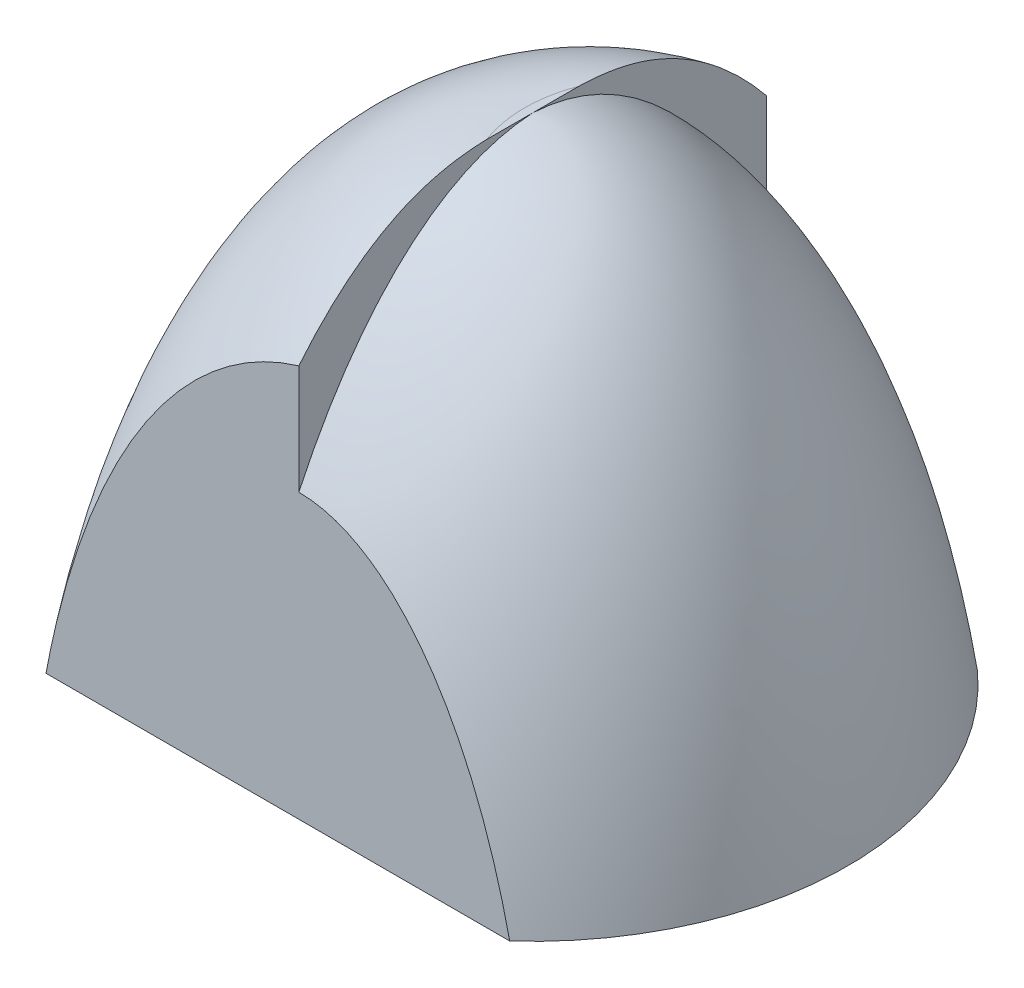
SolidWorks part; units mm, degrees
ref_plane "Front Plane" through (0, 0, 0) normal (0, 0, 1) x (1, 0, 0)
ref_plane "Top Plane" through (0, 0, 0) normal (0, 1, 0) x (1, 0, 0)
ref_plane "Right Plane" through (0, 0, 0) normal (1, 0, 0) x (0, 0, -1)
sketch "Sketch1" plane through (0, 0, 0) normal (0, 0, 1) x (1, 0, 0)
  line L0 (0, 0) -> (91.3948, 0) construction
  line L1 (0, -274.9226) -> (0, 50480.6925) construction
  ellipse E0 centre (0, 0) end of major axis (0, 712.2672) minor radius 343.2806
extrude "Boss-Extrude1" add sketch "Sketch1" along normal blind 237.5 and the other way blind 237.5
sketch "Sketch7" plane through (0, 0, 237.5) normal (0, 0, 1) x (1, 0, 0)
  line L1 (-553.6267, 209.5972) -> (494.8512, 209.5972)
  line L2 (-553.6267, 209.5972) -> (-553.6267, -734.6018)
  line L3 (-553.6267, -734.6018) -> (494.8512, -734.6018)
  line L4 (494.8512, 209.5972) -> (494.8512, -734.6018)
  line L5 (-553.6267, 209.5972) -> (494.8512, -734.6018) construction
  line L6 (-553.6267, -734.6018) -> (494.8512, 209.5972) construction
  ellipse E0 centre (0, 0) end of major axis (0, 712.2672) minor radius 343.2806 construction
  point P0 (-29.3877, -262.5023)
  point P6 (0, 712.2672)
  dimension "D1" = 502.67
extrude "Cut-Extrude2" cut sketch "Sketch7" against normal through all contours L1 L4 L3 L2
sketch "Sketch11" plane through (0, 0, 0) normal (0, 0, 1) x (1, 0, 0)
  line L0 (-343.2806, 0) -> (-743.2267, 0)
  line L1 (-200000, 0) -> (200091.3948, 0) construction
  line L2 (-743.2267, 0) -> (-743.2267, 860.3411)
  line L3 (-743.2267, 860.3411) -> (0, 860.3411)
  line L4 (0, -200274.9226) -> (0, 250480.6925) construction
  line L5 (0, 860.3411) -> (0, 712.2672)
  line L6 (65.7962, 0) -> (65.7962, 545.5092) construction
  ellipse E0 centre (0, 0) end of major axis (0, 712.2672) minor radius 343.2806 construction
  ellipse E1 centre (0, 0) end of major axis (0, 712.2672) minor radius 343.2806 (0, 712.2672) -> (-343.2806, 0) ccw
  dimension "D1" = 409.0768
revolve "Cut-Revolve2" cut sketch "Sketch11" angle 360 about L6
sketch "Sketch15" plane through (0, 0, 0) normal (0, 0, 1) x (1, 0, 0)
  line L0 (0, 0) -> (0, 712.2672) construction
  line L1 (-248.4221, 209.5972) -> (328.0812, 209.5972) construction
  line L2 (0, 209.5972) -> (50000, 209.5972) construction
  line L3 (8.3024, 946.5818) -> (524.826, 946.5818)
  line L4 (8.3024, 243.1848) -> (8.3024, 662.4341) construction
  line L5 (8.3024, 712.0588) -> (8.3024, 946.5818)
  line L6 (524.826, 946.5818) -> (524.826, 209.5972)
  line L7 (524.826, 209.5972) -> (328.0812, 209.5972)
  line L8 (8.3024, 1026.3563) -> (8.3024, 2392.2081) construction
  line L9 (8.3024, 712.0588) -> (8.3024, 946.5818) construction
  ellipse E0 centre (0, 0) end of major axis (0, 712.2672) minor radius 343.2806 construction
  ellipse E1 centre (0, 0) end of major axis (0, 712.2672) minor radius 343.2806 (328.0812, 209.5972) -> (8.3024, 712.0588) ccw
  dimension "D1" = 319.7787
revolve "Cut-Revolve4" cut sketch "Sketch15" angle 90 about L8 other way angle 90
ref_plane "Plane1" through (0, 43.0972, 0) normal (0, -1, 0) x (-1, 0, 0)
